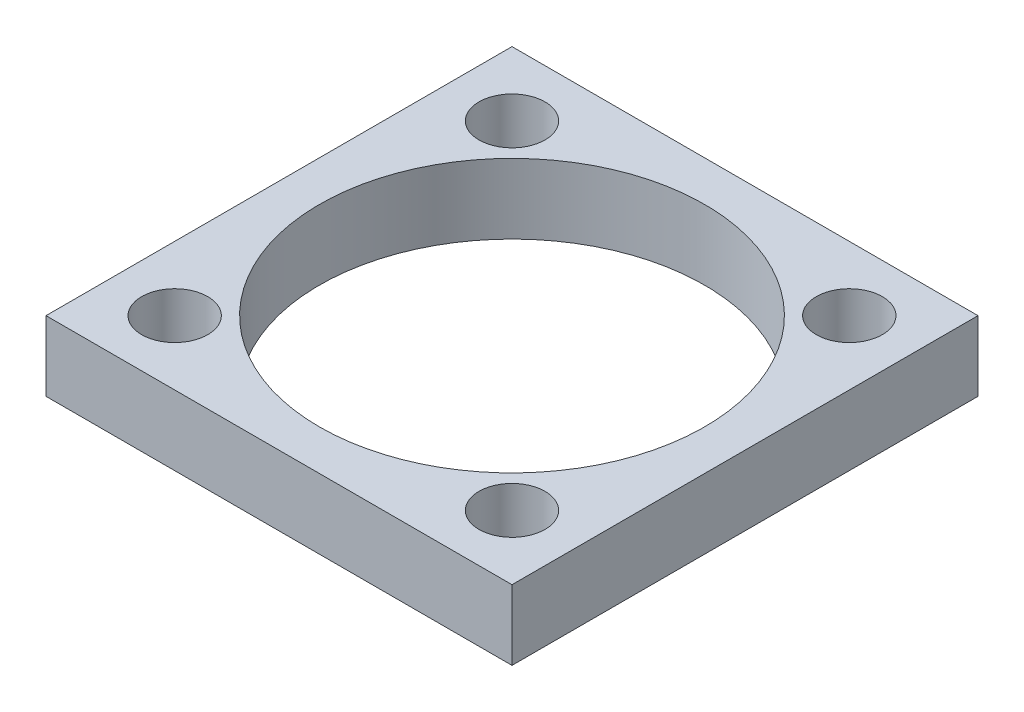
SolidWorks part; units mm, degrees
ref_plane "Front Plane" through (0, 0, 0) normal (0, 0, 1) x (1, 0, 0)
ref_plane "Top Plane" through (0, 0, 0) normal (0, 1, 0) x (1, 0, 0)
ref_plane "Right Plane" through (0, 0, 0) normal (1, 0, 0) x (0, 0, -1)
sketch "Sketch2" plane through (0, 0, 0) normal (0, 1, 0) x (1, 0, 0)
  line L1 (-12.7, -12.7) -> (12.7, -12.7)
  line L2 (-12.7, -12.7) -> (-12.7, 12.7)
  line L3 (-12.7, 12.7) -> (12.7, 12.7)
  line L4 (12.7, -12.7) -> (12.7, 12.7)
  line L5 (-12.7, -12.7) -> (12.7, 12.7) construction
  line L6 (-12.7, 12.7) -> (12.7, -12.7) construction
  point P0 (0, 0)
  dimension "D2" = 25.4
extrude "Boss-Extrude1" add sketch "Sketch2" along normal blind 3.81
sketch "Sketch4" plane through (0, 3.81, 0) normal (0, 1, 0) x (1, 0, 0)
  line L0 (-9.1924, 9.1924) -> (9.1924, -9.1924) construction
  line L1 (-10.5, 0) -> (10.5, 0) construction
  line L2 (9.1924, 9.1924) -> (-9.1924, -9.1924) construction
  circle A0 centre (0, 0) radius 10.5
  point P9 (0, 0)
  point P10 (9.1924, 9.1924)
  point P11 (-9.1924, -9.1924)
  dimension "D3" = 21
  dimension "D1" = 26
  dimension "D2" = 45
  dimension "D4" = 45
extrude "Cut-Extrude1" cut sketch "Sketch4" against normal through all
hole_wizard "M3 Clearance Hole2" positions "3DSketch5" profile "Sketch9" hole size "M3" standard "ANSI Metric" end condition through all
sketch3d "3DSketch5"
  point P0 (-9.1924, 3.81, -9.1924)
  point P3 (9.1924, 3.81, 9.1924)
  point P6 (9.1924, 3.81, -9.1924)
  point P9 (-9.1924, 3.81, 9.1924)
sketch "Sketch9" plane through (-9.1924, 3.81, -9.1924) normal (1, 0, 0) x (0, 0, 1)
  line L0 (0, 0) -> (0, 3.81)
  line L1 (0, 3.81) -> (1.8, 3.81)
  line L2 (1.8, 3.81) -> (1.8, 0)
  line L5 (1.8, 0) -> (0, 0)
  line L11 (0, -6.35) -> (0, 107.95) construction
  dimension "Thru Hole Dia." = 3.6
  dimension "Thru Hole Depth" = 3.81
